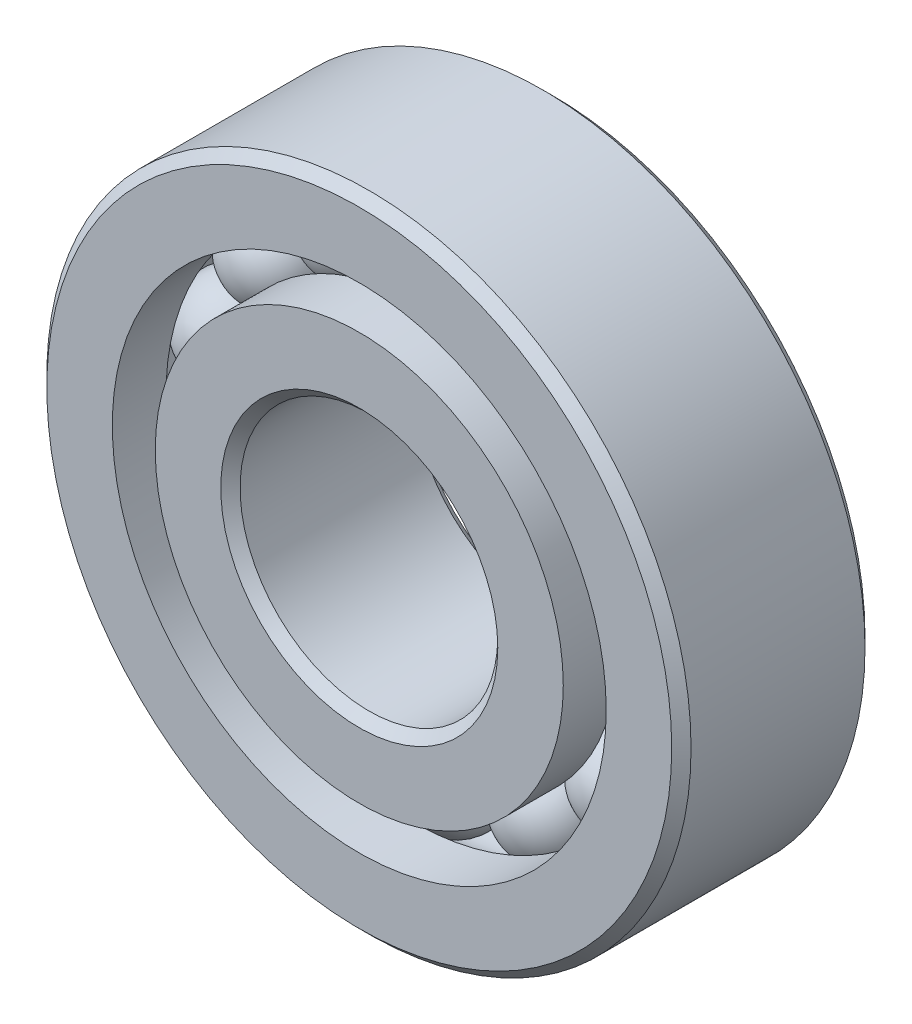
SolidWorks part; units mm, degrees
material "AISI 304"
ref_plane "Front Plane" through (0, 0, 0) normal (0, 0, 1) x (1, 0, 0)
ref_plane "Top Plane" through (0, 0, 0) normal (0, 1, 0) x (1, 0, 0)
ref_plane "Right Plane" through (0, 0, 0) normal (1, 0, 0) x (0, 0, -1)
sketch "Sketch1" plane through (0, 0, 0) normal (1, 0, 0) x (0, 0, -1)
  line L0 (-0.75, 0) -> (0.75, 0) construction
  line L1 (0, 2.5) -> (0, -2.5) construction
  line L2 (0.675, 2.5) -> (-0.675, 2.5)
  line L3 (-0.675, 2.5) -> (-0.75, 2.425)
  line L4 (-0.75, 2.425) -> (-0.75, 1.9167)
  line L5 (-0.75, 1.9167) -> (-0.3333, 1.9167)
  line L6 (0.75, 1.9167) -> (0.3333, 1.9167)
  line L7 (0.75, 2.425) -> (0.75, 1.9167)
  line L8 (0.675, 2.5) -> (0.75, 2.425)
  line L9 (0, 2.5) -> (0, 1.75) construction
  line L10 (0, 1.75) -> (0, 1) construction
  arc A0 (-0.3333, 1.9167) -> (0.3333, 1.9167) centre (0, 1.75) cw
  arc A1 (-0.3333, 1.9167) -> (0.3333, 1.9167) centre (0, 1.75) ccw construction
  point P14 (0, 1)
  point P15 (0, -1)
  dimension "Width" = 1.5
  dimension "OD" = 5
  dimension "D1" = 45
  dimension "D2" = 0.075
  dimension "D3" = 0.6667
  dimension "Shaft Dia" = 2
  dimension "D4" = 0.1667
revolve "Revolve1" add sketch "Sketch1" angle 360 about L0
sketch "Sketch2" plane through (0, 0, 0) normal (1, 0, 0) x (0, 0, -1)
  line L0 (-0.75, 1.5833) -> (-0.3333, 1.5833)
  line L1 (-0.75, 2.425) -> (-0.75, -2.425) construction
  line L2 (-0.75, 1.5833) -> (-0.75, 1.075)
  line L3 (-0.75, 1.075) -> (-0.675, 1)
  line L4 (-0.675, 1) -> (0.675, 1)
  line L5 (0, 2.5) -> (0, -2.5) construction
  line L6 (0, 1) -> (0, 1.3773) construction
  line L7 (0, 1.3773) -> (0, 1) construction
  line L8 (-0.75, 1.5833) -> (-0.75, 0.5667) construction
  line L10 (0.75, 1.5833) -> (0.3333, 1.5833)
  line L11 (0.75, 1.5833) -> (0.75, 1.075)
  line L12 (0.75, 1.075) -> (0.675, 1)
  arc A0 (-0.3333, 1.5833) -> (0.3333, 1.5833) centre (0, 1.75) ccw
  arc A1 (0.3333, 1.9167) -> (-0.3333, 1.9167) centre (0, 1.75) ccw construction
  circle A2 centre (0, 1.75) radius 0.3727 construction
  dimension "D1" = 0.075
  dimension "D2" = 45
revolve "Revolve2" add sketch "Sketch2" angle 360 about L0
sketch "Sketch3" plane through (0, 0, 0) normal (1, 0, 0) x (0, 0, -1)
  line L0 (-0.3727, 1.75) -> (0.3727, 1.75)
  line L1 (0, 1.75) -> (0, 0) construction
  circle A1 centre (0, 1.75) radius 0.3727 construction
  arc A2 (-0.3727, 1.75) -> (0.3727, 1.75) centre (0, 1.75) cw
  arc A3 (0.3333, 1.9167) -> (-0.3333, 1.9167) centre (0, 1.75) ccw construction
  dimension "D1" = 0.7454
  dimension "D2" = 1.75
revolve "Revolve3" add sketch "Sketch3" angle 360 about L0
ref_axis "Axis1" through (0, 0, -0.75) along (0, 0, 1)
pattern_circular "CirPattern1" count 14 every 25.714 about axis through (0, 0, -0.75) along (0, 0, 1) of bodies 104
sketch "Sketch6" plane through (0, 0, 0) normal (0, 1, 0) x (1, 0, 0)
  point P0 (2.5, -0.75)
  point P1 (2.5, 0.75)
  dimension "D1" = 1.5
ref_axis "Center Axis 1" through (0, 0, -1.2081) along (0, 0, 1)
ref_plane "Contact Plane 1" through (0, 0, 0.75) normal (0, 0, 1) x (1, 0, 0)
ref_plane "Contact Plane 2" through (0, 0, -0.75) normal (0, 0, -1) x (-1, 0, 0)
equation "\"D2@Sketch1\" = \"Width@Sketch1\"*.05"
equation "\"D3@Sketch1\" = \"Width@Sketch1\"/2.25"
equation "\"D4@Sketch1\" = \"D3@Sketch1\"/4"
equation "\"Balls@CirPattern1\"=\"D2@Sketch3\"*2*pi/\"D1@Sketch3\"-1"
equation "\"D2@CirPattern1\" = 360/\"Balls@CirPattern1\""
equation "\"D1@Sketch2\"=\"D2@Sketch1\""
equation "\"D1@Sketch6\"=\"Width@Sketch1\""
